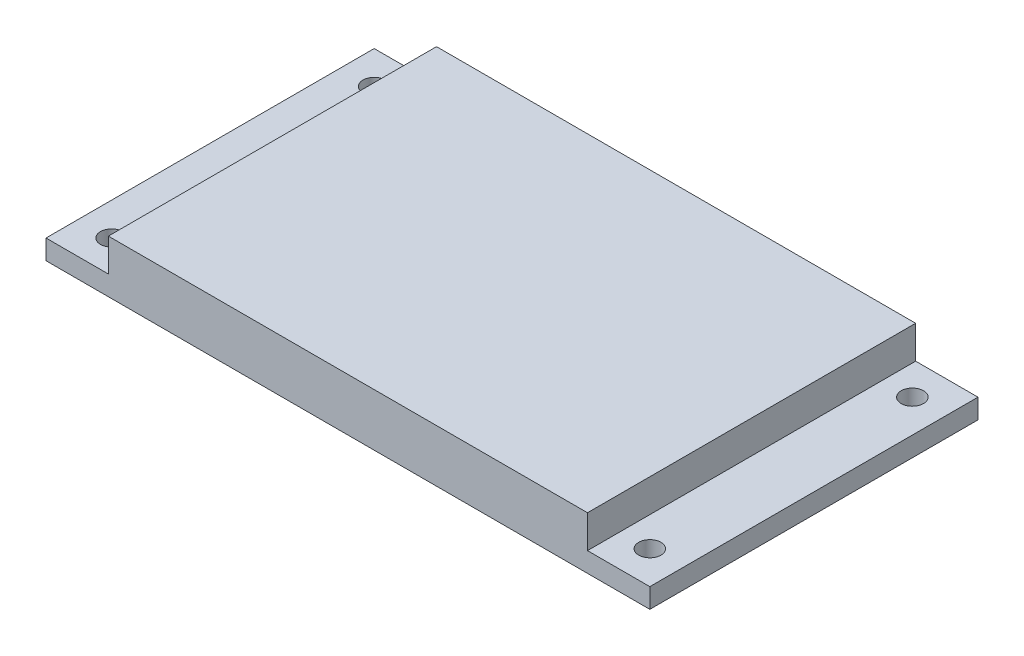
SolidWorks part; units mm, degrees
ref_plane "Front Plane" through (0, 0, 0) normal (0, 0, 1) x (1, 0, 0)
ref_plane "Top Plane" through (0, 0, 0) normal (0, 1, 0) x (1, 0, 0)
ref_plane "Right Plane" through (0, 0, 0) normal (1, 0, 0) x (0, 0, -1)
sketch "Sketch1" plane through (0, 0, 0) normal (0, 1, 0) x (1, 0, 0)
  line L1 (-36.5, -25) -> (36.5, -25)
  line L2 (-36.5, -25) -> (-36.5, 25)
  line L3 (-36.5, 25) -> (36.5, 25)
  line L4 (36.5, -25) -> (36.5, 25)
  line L5 (-36.5, -25) -> (36.5, 25) construction
  line L6 (-36.5, 25) -> (36.5, -25) construction
  point P0 (0, 0)
  dimension "D1" = 73
  dimension "D2" = 50
extrude "Boss-Extrude1" add sketch "Sketch1" along normal blind 5
sketch "Sketch2" plane through (0, 0, 0) normal (0, -1, 0) x (1, 0, 0)
  line L0 (-36.5, 25) -> (36.5, 25) construction
  line L1 (-46, -25) -> (46, -25)
  line L2 (-46, -25) -> (-46, 25)
  line L3 (-46, 25) -> (46, 25)
  line L4 (46, -25) -> (46, 25)
  line L5 (-46, -25) -> (46, 25) construction
  line L6 (-46, 25) -> (46, -25) construction
  point P0 (0, 0)
  dimension "D1" = 92
extrude "Boss-Extrude2" add sketch "Sketch2" along normal blind 3
sketch "Sketch3" plane through (0, 0, 0) normal (0, 1, 0) x (1, 0, 0)
  line L1 (-40.5, -15.25) -> (40.5, -15.25)
  line L2 (-40.5, -15.25) -> (-40.5, 15.25)
  line L3 (-40.5, 15.25) -> (40.5, 15.25)
  line L4 (40.5, -15.25) -> (40.5, 15.25)
  line L5 (-40.5, -15.25) -> (40.5, 15.25) construction
  line L6 (-40.5, 15.25) -> (40.5, -15.25) construction
  point P0 (0, 0)
  dimension "D1" = 30.5
  dimension "D2" = 81
hole_wizard "M3 Clearance Hole1" positions "Sketch7" profile "Sketch8" hole size "M3" standard "ANSI Metric"
sketch "Sketch7" plane through (0, 0, 0) normal (0, 1, 0) x (1, 0, 0)
  line L0 (-46, 25) -> (-36.5, 25) construction
  line L1 (36.5, 25) -> (46, 25) construction
  line L2 (46, -25) -> (36.5, -25) construction
  line L3 (-36.5, -25) -> (-46, -25) construction
  line L4 (-46, -25) -> (-46, 25) construction
  line L5 (46, 25) -> (46, -25) construction
  point P0 (-41, 20)
  point P2 (-41, -20)
  point P4 (41, 20)
  point P6 (41, -20)
  dimension "D1" = 5
  dimension "D2" = 5
  dimension "D3" = 5
  dimension "D4" = 5
  dimension "D5" = 5
  dimension "D6" = 5
sketch "Sketch8" plane through (-41, 0, -20) normal (1, 0, 0) x (0, 0, 1)
  line L0 (0, 0) -> (0, 11.0215)
  line L1 (0, 11.0215) -> (1.7, 10)
  line L2 (1.7, 10) -> (1.7, 0)
  line L5 (1.7, 0) -> (0, 0)
  line L10 (0, 11.0215) -> (-1.7, 10) construction
  line L11 (0, -6.35) -> (0, 107.95) construction
  dimension "Hole Dia." = 3.4
  dimension "Hole Depth" = 10
  dimension "Drill Angle" = 118
equation "\"8`\"=84.8464"
